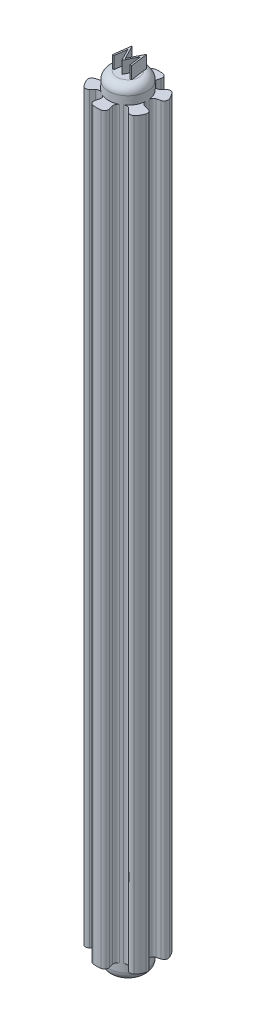
SolidWorks part; units mm, degrees
ref_plane "Front Plane" through (0, 0, 0) normal (0, 0, 1) x (1, 0, 0)
ref_plane "Top Plane" through (0, 0, 0) normal (0, 1, 0) x (1, 0, 0)
ref_plane "Right Plane" through (0, 0, 0) normal (1, 0, 0) x (0, 0, -1)
sketch "Sketch2" plane through (0, 0, 0) normal (0, 1, 0) x (1, 0, 0)
  line L0 (0, 0) -> (0.0739, 0)
  line L2 (2.3008, -0.5891) -> (3.7752, -0.9786)
  line L3 (0.0739, 0) -> (0.1042, -0.0303)
  line L4 (0, 0) -> (0.0858, -0.0446)
  line L5 (1.6802, 1.6786) -> (2.7413, 2.7388)
  line L6 (-1.6794, 1.6794) -> (-2.74, 2.74)
  line L8 (0.6147, 2.2941) -> (1.0029, 3.743)
  line L9 (-0.6147, 2.2941) -> (-1.0029, 3.743)
  line L10 (2.2941, 0.6147) -> (3.743, 1.0029)
  line L11 (0, 0) -> (0.1042, -0.0303)
  line L12 (-2.2941, 0.6147) -> (-3.743, 1.0029)
  line L13 (0.0739, 0) -> (0.0858, -0.0446)
  line L14 (-0.6147, -2.2941) -> (-1.0029, -3.743)
  line L15 (-2.2941, -0.6147) -> (-3.743, -1.0029)
  line L16 (-1.6794, -1.6794) -> (-2.74, -2.74)
  line L17 (0.6814, -2.2752) -> (1.0684, -3.7248)
  line L18 (1.7145, -1.6435) -> (2.7672, -2.6981)
  arc A0 (-2.2941, 0.6147) -> (-2.2941, -0.6147) centre (0, 0) ccw
  arc A1 (-2.74, 2.74) -> (-3.743, 1.0029) centre (0, 0) ccw
  arc A2 (1.0029, 3.743) -> (-1.0029, 3.743) centre (0, 0) ccw
  arc A3 (3.743, 1.0029) -> (2.7413, 2.7388) centre (0, 0) ccw
  arc A5 (-1.0029, -3.743) -> (1.0684, -3.7248) centre (0, 0) ccw
  arc A6 (-3.743, -1.0029) -> (-2.74, -2.74) centre (0, 0) ccw
  arc A7 (-2.74, 2.74) -> (-3.743, 1.0029) centre (0, 0) ccw
  arc A8 (1.0029, 3.743) -> (-1.0029, 3.743) centre (0, 0) ccw
  arc A9 (3.743, 1.0029) -> (2.7413, 2.7388) centre (0, 0) ccw
  arc A10 (-3.743, -1.0029) -> (-2.74, -2.74) centre (0, 0) ccw
  arc A11 (-1.0029, -3.743) -> (1.0684, -3.7248) centre (0, 0) ccw
  arc A12 (2.7672, -2.6981) -> (3.7752, -0.9786) centre (1.7753, -0.9614) ccw
  arc A13 (-0.6147, 2.2941) -> (-1.6794, 1.6794) centre (0, 0) ccw
  arc A14 (1.6802, 1.6786) -> (0.6147, 2.2941) centre (0, 0) ccw
  arc A15 (2.3008, -0.5891) -> (2.2941, 0.6147) centre (0, 0) ccw
  arc A16 (0.6814, -2.2752) -> (1.7145, -1.6435) centre (0, 0) ccw
  arc A17 (-1.6794, -1.6794) -> (-0.6147, -2.2941) centre (0, 0) ccw
  dimension "D1" = 3.875
  dimension "D2" = 2.375
extrude "Boss-Extrude1" add sketch "Sketch2" along normal blind 91.5 contours L16 A17 L14 A5 L17 A16 L18 A12 L2 A15 L10 A3 L5 A14 L8 A2 L9 A13 L6 A1 L12 A0 L15 A6 L11 L13 L4 L0 L3 region at (0.0225, 0, 0.0171)
sketch "Sketch3" plane through (0, 0, 0) normal (0, -1, 0) x (1, 0, 0)
  circle A0 centre (0, 0) radius 2.375
  dimension "D1" = 4.75
extrude "Boss-Extrude2" add sketch "Sketch3" along normal blind 2
sketch "Sketch4" plane through (0, 91.5, 0) normal (0, 1, 0) x (1, 0, 0)
  circle A0 centre (0, 0) radius 2.375
  dimension "D1" = 4.75
extrude "Boss-Extrude3" add sketch "Sketch4" along normal blind 2
fillet "Fillet1" radius 0.5 24 edges at (-2.74, 45.75, -2.74) (-1.6794, 45.75, -1.6794) (-0.6147, 45.75, -2.2941) (-1.0029, 45.75, -3.743) (1.0029, 45.75, -3.743) (0.6147, 45.75, -2.2941) (1.6802, 45.75, -1.6786) (2.7413, 45.75, -2.7388) (3.743, 45.75, -1.0029) (2.2941, 45.75, -0.6147) (2.3008, 45.75, 0.5891) (3.7752, 45.75, 0.9786) (2.7672, 45.75, 2.6981) (1.7145, 45.75, 1.6435) (0.6814, 45.75, 2.2752) (-1.6794, 45.75, 1.6794) (-2.2941, 45.75, 0.6147) (-2.2941, 45.75, -0.6147) (-0.6147, 45.75, 2.2941) (-3.743, 45.75, -1.0029) (-3.743, 45.75, 1.0029) (-2.74, 45.75, 2.74) (-1.0029, 45.75, 3.743) (1.0684, 45.75, 3.7248)
sketch "Sketch5" plane through (0, 93.5, 0) normal (0, 1, 0) x (1, 0, 0)
  text T0 "M" font "Century Gothic" height in points 8
sketch "Sketch6" plane through (0, -2, 0) normal (0, -1, 0) x (1, 0, 0)
  circle A0 centre (0, 0) radius 1
  dimension "D1" = 2
extrude "Cut-Extrude4" cut sketch "Sketch6" against normal blind 0.5 draft 50
extrude "Boss-Extrude4" add sketch "Sketch5" along normal blind 1.5
fillet "Fillet2" radius 1 2 edges at (0, 93.5, 2.375) (0, -2, -2.375)
